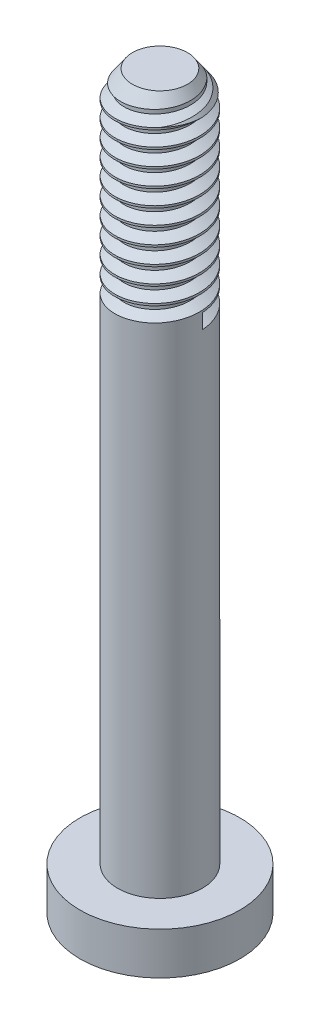
SolidWorks part; units mm, degrees
ref_plane "Front Plane" through (0, 0, 0) normal (0, 0, 1) x (1, 0, 0)
ref_plane "Top Plane" through (0, 0, 0) normal (0, 1, 0) x (1, 0, 0)
ref_plane "Right Plane" through (0, 0, 0) normal (1, 0, 0) x (0, 0, -1)
sketch "Sketch1" plane through (0, 0, 0) normal (0, 0, 1) x (1, 0, 0)
  line L1 (3, 0) -> (3, 1.5875)
  line L2 (3, 1.5875) -> (1.5875, 1.5875)
  line L3 (1.5875, 1.5875) -> (1.5875, 27.431)
  line L4 (1.5875, 27.431) -> (0, 27.431)
  line L5 (0, 27.431) -> (0, 0)
  line L6 (0, 0) -> (3, 0)
  line L7 (0, 0) -> (0, -2.6248) construction
  point P4 (0, 0)
  dimension "D1" = 6
  dimension "D2" = 3.175
  dimension "D3" = 27.431
  dimension "D4" = 1.5875
revolve "Revolve1" add sketch "Sketch1" angle 360 about L7
chamfer "Chamfer1" distance 0.7937 angle 35 1 edges at (0, 27.431, 1.5875) first distance on face at (0, 27.431, 1.5875)
thread "Thread1" pitch 0.635 method cut profile "Thread Profile1" start angle 0, offset 1.5875, length 7.9375, pitch 0.635, diameter 3.175
ref_plane "Plane1" through (-1.5875, 28.2247, 0) normal (0, 0, 1) x (-1, 0, 0)
sketch "Thread Profile1" plane through (-1.5875, 28.2247, 0) normal (0, 0, 1) x (-1, 0, 0)
  line L0 (0, 0) -> (0, 0.635) construction
  line L11 (0, 0) -> (0, 0.5556)
  line L12 (0, 0.5556) -> (-0.3437, 0.3572)
  line L13 (-0.3437, 0.3572) -> (-0.3437, 0.1984)
  line L15 (-0.3437, 0.1984) -> (0, 0)
  line L17 (-0.3437, 0.2778) -> (0, 0.2778) construction
  point P2 (0, 0)
  dimension "Pitch" = 0.635
  dimension "Profile_Angle" = 60
  dimension "Profile_Land" = 0.1588
  dimension "Profile_Height" = 0.3437
